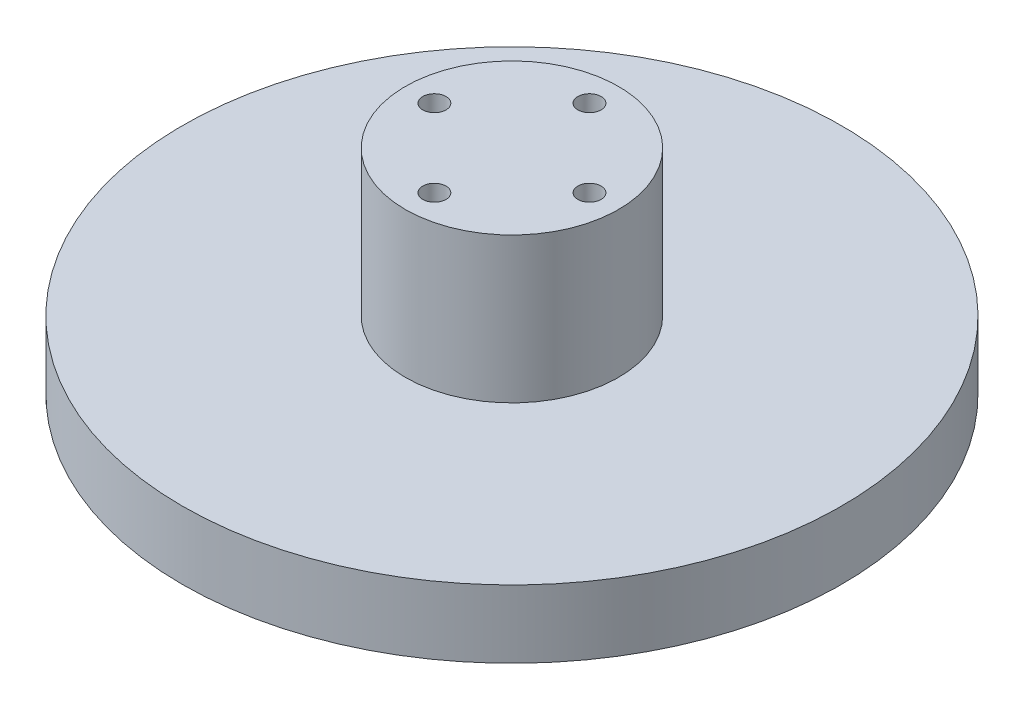
SolidWorks part; units mm, degrees
ref_plane "Front Plane" through (0, 0, 0) normal (0, 0, 1) x (1, 0, 0)
ref_plane "Top Plane" through (0, 0, 0) normal (0, 1, 0) x (1, 0, 0)
ref_plane "Right Plane" through (0, 0, 0) normal (1, 0, 0) x (0, 0, -1)
sketch "Sketch1" plane through (0, 0, 0) normal (0, 1, 0) x (1, 0, 0)
  circle A0 centre (0, 0) radius 34
  dimension "D1" = 68
extrude "Boss-Extrude1" add sketch "Sketch1" along normal blind 7
sketch "Sketch2" plane through (0, 7, 0) normal (0, 1, 0) x (1, 0, 0)
  circle A0 centre (0, 0) radius 11
  dimension "D1" = 22
extrude "Boss-Extrude2" add sketch "Sketch2" along normal blind 15
sketch "Sketch4" plane through (0, 0, 0) normal (0, -1, 0) x (1, 0, 0)
  line L0 (-8, 0) -> (0, 0) construction
  circle A0 centre (-8, 0) radius 2.25
  dimension "D1" = 4.5
  dimension "D2" = 8
extrude "Cut-Extrude1" cut sketch "Sketch4" against normal offset from surface (19 mm away) 3 up to face at (0, 22, 11)
hole_wizard "CSK for M2 Countersunk Flat Head Screw1" positions "3DSketch1" profile "Sketch5" countersink size "M2" standard "ISO" end condition through all
sketch3d "3DSketch1"
  line L0 (-8, 19, 0) -> (-8, 0, 0) construction
  point P0 (-8, 19, 0)
sketch "Sketch5" plane through (-8, 19, 0) normal (1, 0, 0) x (0, 0, -1)
  line L0 (0, 0) -> (0, 3)
  line L1 (0, 3) -> (1.2, 3)
  line L2 (1.2, 3) -> (1.2, 1)
  line L3 (1.2, 1) -> (2.2, 0)
  line L5 (2.2, 0) -> (0, 0)
  line L6 (-1.2, 1) -> (-2.2, 0) construction
  line L11 (0, -6.35) -> (0, 107.95) construction
  dimension "Thru Hole Dia." = 2.4
  dimension "Thru Hole Depth" = 3
  dimension "Near C'Sink Dia." = 4.4
  dimension "Near C'Sink Angle" = 90
pattern_circular "CirPattern1" count 4 over 360 about axis through (0, 7, 0) along (0, -1, 0) of "CSK for M2 Countersunk Flat Head Screw1", "Cut-Extrude1"
